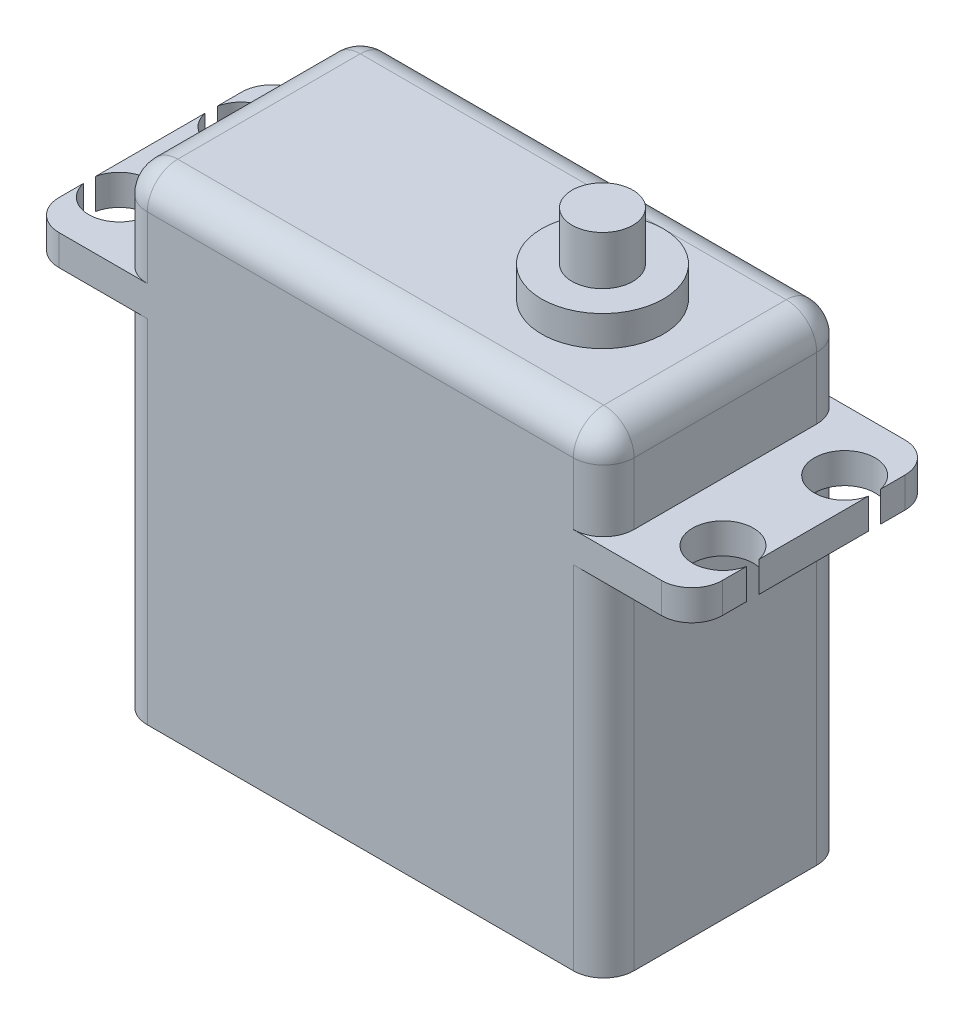
SolidWorks part; units mm, degrees
ref_plane "Front Plane" through (0, 0, 0) normal (0, 0, 1) x (1, 0, 0)
ref_plane "Top Plane" through (0, 0, 0) normal (0, 1, 0) x (1, 0, 0)
ref_plane "Right Plane" through (0, 0, 0) normal (1, 0, 0) x (0, 0, -1)
sketch "Sketch1" plane through (0, 0, 0) normal (0, 1, 0) x (1, 0, 0)
  line L1 (0, 0) -> (40, 0)
  line L2 (0, 0) -> (0, 20)
  line L3 (0, 20) -> (40, 20)
  line L4 (40, 0) -> (40, 20)
  dimension "D1" = 40
  dimension "D2" = 20
extrude "Boss-Extrude1" add sketch "Sketch1" along normal blind 39
ref_plane "Plane1" through (0, 28.9, 0) normal (0, -1, 0) x (-1, 0, 0)
sketch "Sketch2" plane through (0, 28.9, 0) normal (0, -1, 0) x (-1, 0, 0)
  line L1 (-47.25, 20) -> (7.25, 20)
  line L2 (-47.25, 20) -> (-47.25, 0)
  line L3 (-47.25, 0) -> (7.25, 0)
  line L4 (7.25, 20) -> (7.25, 0)
  line L5 (-40, 20) -> (0, 20) construction
  line L7 (0, 0) -> (-40, 0) construction
  line L8 (-44.8, 15) -> (-44.8, 5) construction
  circle A0 centre (-44.8, 15) radius 2.5
  circle A1 centre (-44.8, 5) radius 2.5
  circle A2 centre (4.8, 15) radius 2.5
  circle A3 centre (4.8, 5) radius 2.5
  point P6 (-20, 0)
  point P8 (-20, 20)
  point P18 (-44.8, 10)
  point P19 (-47.25, 10)
  point P20 (0, 0)
  point P21 (-43.451, 15)
  point P22 (0, 0)
  point P23 (-44.5609, 15)
  point P24 (-44.7244, 15)
  dimension "D2" = 5
  dimension "D1" = 54.5
  dimension "D3" = 49.6
  dimension "D4" = 10
  dimension "D5" = 2.45
extrude "Boss-Extrude2" add sketch "Sketch2" against normal blind 2.5 contours L8 A0 L2 A1 | A0 L8 A1 L2 L3 L4 A3 A2 L1 region at (19.6142, 28.9, -10) region at (46.1372, 28.9, -10)
fillet "Fillet1" radius 2.5 4 edges at (-7.25, 30.15, 0) (-7.25, 30.15, -20) (47.25, 30.15, -20) (47.25, 30.15, 0)
sketch "Sketch3" plane through (0, 39, 0) normal (0, 1, 0) x (1, 0, 0)
  line L0 (47.25, 14.5025) -> (47.25, 5.4975) construction
  circle A0 centre (29.9, 10) radius 5
  arc A1 (47.25, 15.4975) -> (47.25, 14.5025) centre (44.8, 15) ccw construction
  point P2 (47.25, 10)
  point P3 (0, 0)
  dimension "D1" = 10
  dimension "D2" = 14.9
extrude "Boss-Extrude3" add sketch "Sketch3" along normal blind 2.5
sketch "Sketch4" plane through (0, 41.5, 0) normal (0, 1, 0) x (1, 0, 0)
  circle A0 centre (29.9, 10) radius 2.5
  circle A1 centre (29.9, 10) radius 5 construction
  dimension "D1" = 5
extrude "Boss-Extrude4" add sketch "Sketch4" along normal blind 4
fillet "Fillet2" radius 2.5 10 edges at (20, 39, 0) (20, 39, -20) (0, 35.2, -20) (0, 14.45, -20) (40, 14.45, -20) (40, 35.2, -20) (0, 35.2, 0) (0, 14.45, 0) (40, 14.45, 0) (40, 35.2, 0)
fillet "Fillet3" radius 2.5 6 edges at (0.7322, 38.2678, -19.2678) (0.7322, 38.2678, -0.7322) (39.2678, 38.2678, -0.7322) (39.2678, 38.2678, -19.2678) (0, 39, -10) (40, 39, -10)
